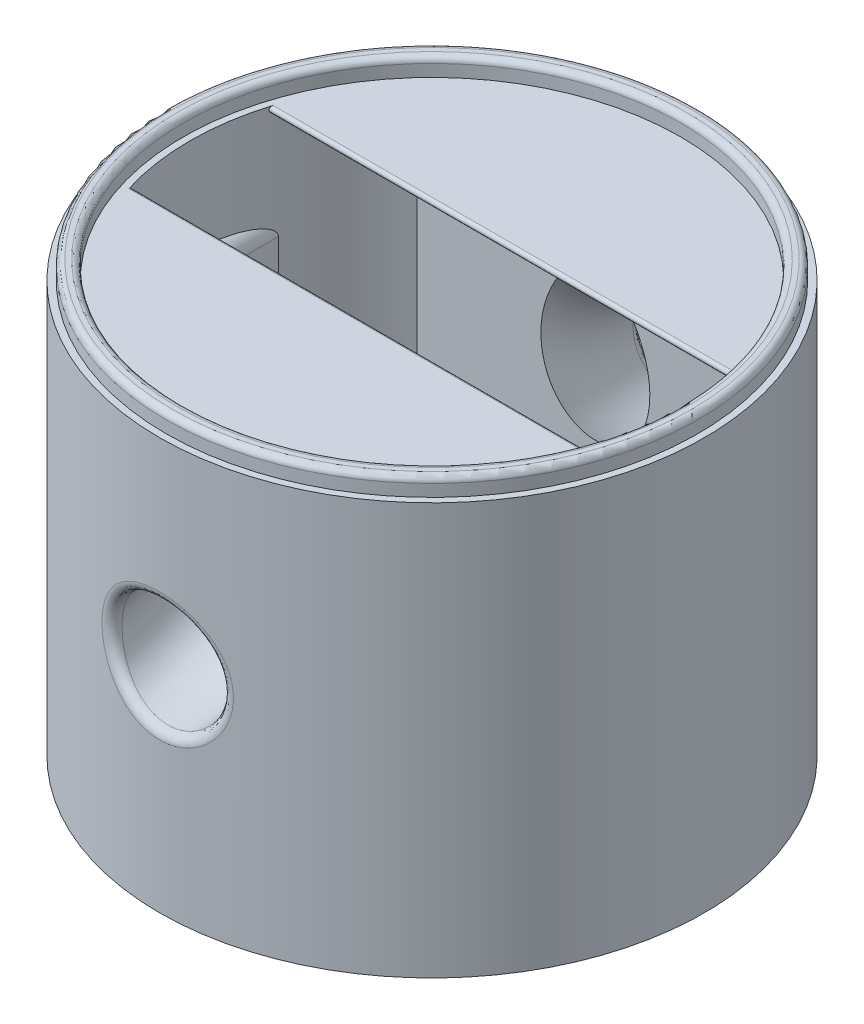
SolidWorks part; units mm, degrees
ref_plane "Płaszczyzna przednia" through (0, 0, 0) normal (0, 0, 1) x (1, 0, 0)
ref_plane "Płaszczyzna górna" through (0, 0, 0) normal (0, 1, 0) x (1, 0, 0)
ref_plane "Płaszczyzna prawa" through (0, 0, 0) normal (1, 0, 0) x (0, 0, -1)
sketch "Sketch1" plane through (0, 0, 0) normal (0, 1, 0) x (1, 0, 0)
  circle A0 centre (0, 0) radius 45
extrude "Boss-Extrude1" add sketch "Sketch1" along normal blind 35
sketch "Sketch19" plane through (0, 35, 0) normal (0, 1, 0) x (1, 0, 0)
  circle A0 centre (0, 0) radius 40
extrude "Cut-Extrude1" cut sketch "Sketch19" against normal blind 56
sketch "Sketch20" plane through (0, 35, 0) normal (0, 1, 0) x (1, 0, 0)
  line L0 (0, 0) -> (-40, 0)
  line L1 (-40, 0) -> (-40, 15)
  line L2 (-40, 15) -> (-37.9667, 15)
  line L3 (-37.9667, 15) -> (-37.9667, -15.0048)
  line L4 (0, 0) -> (0, -15.0048)
  line L5 (-37.9667, -15.0048) -> (-40, -15.0048)
  line L6 (-37.9667, -15.0048) -> (-37.9667, 15)
  line L7 (-37.9667, 15) -> (-40, 15)
  line L8 (-40, -15.0048) -> (-40, 15)
  line L9 (40, 15) -> (37.9667, 15)
  line L10 (37.9667, 15) -> (37.9667, -15.0048)
  line L11 (40, -15.0048) -> (40, 15)
  line L12 (37.9667, -15.0048) -> (40, -15.0048)
  line L13 (0, 0) -> (-15, 0)
  line L14 (-15, 0) -> (-15, -40)
  line L15 (-15, -40) -> (15, -40)
  line L16 (15, -40) -> (15, 40)
  line L17 (-15, 40) -> (-15, 0)
  line L18 (15, 40) -> (-15, 40)
  line L19 (0, 0) -> (0, -10)
  line L20 (0, 0) -> (0, -11)
  line L21 (0, -11) -> (15, -11)
  line L22 (15, -11) -> (15, 11)
  line L23 (15, 11) -> (-15, 11)
  line L24 (-15, 11) -> (-15, -11)
  line L25 (-15, -11) -> (0, -11)
  line L26 (15, -11) -> (15, 11)
  line L28 (-15, -11) -> (15, -11)
  line L29 (-15, -11) -> (-15, -40)
  line L30 (-15, -40) -> (15, -40)
  line L31 (15, -11) -> (15, -40)
  line L32 (15, 40) -> (-15, 40)
  line L33 (15, 40) -> (15, 11)
  line L34 (15, 11) -> (-15, 11)
  line L35 (-15, 40) -> (-15, 11)
  circle A0 centre (0, 0) radius 40 construction
  circle M8 centre (0, 0) radius 40
  dimension "D1" = 40
  dimension "D2" = 40
extrude "Boss-Extrude29" add sketch "Sketch20" along normal blind 1 and the other way blind 10 contours L3 L0 M8 | L8 L5 L3 M8 | L3 L2 L1 M8 | L3 L0 M8 | L10 L12 L11 L9
sketch "Sketch21" plane through (0, 35, 0) normal (0, 1, 0) x (1, 0, 0)
  line L0 (-0.2322, 0) -> (-15.2322, 0)
  line L1 (-0.2322, 0) -> (14.7678, 0)
  line L2 (-15.2322, 0) -> (-15.2322, -40)
  line L3 (-15.2322, -40) -> (14.7678, -40)
  line L4 (14.7678, -40) -> (14.7678, 40)
  line L5 (14.7678, 40) -> (-15.2322, 40)
  line L6 (-15.2322, 40) -> (-15.2322, 0)
  line L7 (14.7678, 0) -> (14.7678, 10.5)
  line L8 (14.7678, 10.5) -> (-15.2322, 10.5)
  line L9 (-15.2322, 10.5) -> (-15.2322, -10.5)
  line L10 (-15.2322, -10.5) -> (14.7678, -10.5)
  line L12 (14.7678, -40) -> (-15.2322, -40)
  line L13 (14.7678, -40) -> (14.7678, -10.5)
  line L14 (14.7678, -10.5) -> (-15.2322, -10.5)
  line L15 (-15.2322, -40) -> (-15.2322, -10.5)
  line L16 (-15.2322, 40) -> (14.7678, 40)
  line L17 (-15.2322, 40) -> (-15.2322, 10.5)
  line L18 (-15.2322, 10.5) -> (14.7678, 10.5)
  line L19 (14.7678, 40) -> (14.7678, 10.5)
sketch "Sketch23" plane through (0, 35, 0) normal (0, 1, 0) x (1, 0, 0)
  circle A0 centre (0, 0) radius 45
  circle A1 centre (0, 0) radius 40
extrude "Boss-Extrude32" add sketch "Sketch23" along normal blind 17
sketch "Sketch24" plane through (-37.9667, 0, 0) normal (1, 0, 0) x (0, 0, -1)
  line L0 (-12.5907, 36) -> (-12.5907, 25) construction
  line L1 (-12.5907, 36) -> (12.5907, 36)
  line L2 (-12.5907, 36) -> (-12.5907, 25)
  line L3 (-12.5907, 25) -> (12.5907, 25)
  line L4 (12.5907, 36) -> (12.5907, 25)
  line L5 (12.5907, 36) -> (-12.5907, 36) construction
  line L6 (-12.5907, 25) -> (12.5907, 25) construction
  line L7 (12.5907, 25) -> (12.5907, 36) construction
  line L8 (-12.5907, 36) -> (12.5907, 25)
  line L9 (0, 30.5) -> (0, 17)
  line L14 (0, 17) -> (-42.6389, 17)
  line L19 (-42.6389, 17) -> (-42.6389, 52)
  line L20 (40, 52) -> (-40, 52) construction
  line L21 (0, 16.95) -> (42.969, 16.95)
  line L23 (42.969, 16.95) -> (-42.6389, 16.95)
  line L24 (42.969, 16.95) -> (42.969, 52)
  line L25 (42.969, 52) -> (-42.6389, 52)
  line L26 (-42.6389, 16.95) -> (-42.6389, 52)
  circle A1 centre (0, 17) radius 36
extrude "Boss-Extrude37" add sketch "Sketch24" along normal blind 80 and the other way blind 5 contours A1 L25 L26 | A1 L24 L25
sketch "Sketch25" plane through (0, 52, 0) normal (0, 1, 0) x (1, 0, 0)
  circle A0 centre (0, 0) radius 9
extrude "Cut-Extrude2" cut sketch "Sketch25" against normal blind 4
sketch "Sketch28" plane through (0, 0, 0) normal (0, -1, 0) x (1, 0, 0)
  circle A0 centre (0, 0) radius 81.8752
  circle A1 centre (0, 0) radius 45
extrude "Cut-Extrude3" cut sketch "Sketch28" against normal blind 125 contours A0 | A1
sketch "Sketch29" plane through (0, 52, 0) normal (0, 1, 0) x (1, 0, 0)
  line L0 (0, 0) -> (-9.1, 0)
  line L1 (-9.1, 0) -> (-9.1, -48)
  line L2 (-9.1, 42.2639) -> (9.1, 42.2639)
  line L3 (-9.1, -48) -> (9.1, -48)
  line L4 (-9.1, -48) -> (-9.1, -42.2639)
  line L5 (-9.1, -42.2639) -> (9.1, -42.2639)
  line L6 (9.1, -48) -> (9.1, -42.2639)
  line L7 (9.1, 48) -> (9.1, 42.2639)
  line L8 (-9.1, 48) -> (9.1, 48)
  line L9 (-9.1, 48) -> (-9.1, 42.2639)
  circle M15 centre (0, 0) radius 45
extrude "Boss-Extrude38" add sketch "Sketch29" against normal blind 52 contours L8 L9 L7 M15 | L3 L6 L1 M15 | L9 L2 L7 M15 | L6 L5 L1 M15
sketch "Sketch32" plane through (0, 0, 48) normal (0, 0, 1) x (1, 0, 0)
  line L0 (0, 0) -> (-66.2271, 0)
  line L1 (-9.1, 0) -> (9.1, 0) construction
  line L3 (-66.2271, 0) -> (66.2271, 0)
  line L4 (-66.2271, 0) -> (-66.2271, 45.6022)
  line L5 (-66.2271, 45.6022) -> (66.2271, 45.6022)
  line L6 (66.2271, 0) -> (66.2271, 45.6022)
  line M6 (-9.1, 52) -> (-9.1, 0)
  line M7 (-9.1, 0) -> (9.1, 0)
  line M8 (9.1, 0) -> (9.1, 52)
extrude "Boss-Extrude41" add sketch "Sketch32" against normal blind 21 contours L5 L4 L0 M6 | L5 M6 M7 M8 | L3 L6 L5 M8
sketch "Sketch30" plane through (0, 0, 48) normal (0, 0, 1) x (1, 0, 0)
  line L0 (-9.1, 19) -> (9.1, 19)
  line L1 (-9.1, 45.6022) -> (-9.1, 52) construction
  line L2 (9.1, 52) -> (9.1, 45.6022) construction
  line L3 (0, 19) -> (0, 25.0181)
  line L4 (0, 25.0181) -> (7.01, 25.0181)
  line L5 (7.01, 25.0181) -> (-5.4249, 25.0181)
  line L6 (0, 19) -> (0, 0)
  circle A0 centre (0, 19) radius 9
revolve "Cut-Revolve4" cut sketch "Sketch30" angle 62
sketch "Sketch33" plane through (0, 0, -48) normal (0, 0, -1) x (-1, 0, 0)
  line L0 (0, 0) -> (68.0647, 0)
  line L2 (68.0647, 0) -> (-74.072, 0)
  line L3 (68.0647, 0) -> (68.0647, 43.8772)
  line L4 (68.0647, 43.8772) -> (-74.072, 43.8772)
  line L5 (-74.072, 0) -> (-74.072, 43.8772)
  line M6 (-9.1, 52) -> (-9.1, 0)
  line M7 (-9.1, 0) -> (9.1, 0)
  line M8 (9.1, 0) -> (9.1, 52)
extrude "Boss-Extrude42" add sketch "Sketch33" against normal blind 21 contours L5 L2 L4 M6 | L3 L4 L0 M8 | L4 M8 M6 M7
sketch "Sketch34" plane through (0, 0, -48) normal (0, 0, -1) x (-1, 0, 0)
  line L0 (9.1, 43.8772) -> (9.1, 0)
  line L1 (36, 43.8772) -> (9.1, 43.8772) construction
  line L2 (9.1, 43.8772) -> (9.1, 52) construction
  line L3 (68.0647, 0) -> (-74.072, 0) construction
  line L4 (-9.1, 43.8772) -> (-9.1, 0)
  line L5 (-9.1, 43.8772) -> (-36, 43.8772) construction
  line L6 (-9.1, 52) -> (-9.1, 43.8772) construction
  line L7 (0, 0) -> (0, 19)
  circle A0 centre (0, 19) radius 9
revolve "Cut-Revolve5" cut sketch "Sketch34" angle 63
sketch "Sketch35" plane through (0, 52, 0) normal (0, 1, 0) x (1, 0, 0)
  circle A0 centre (0, 0) radius 102.54
  circle A1 centre (0, 0) radius 45
extrude "Cut-Extrude4" cut sketch "Sketch35" against normal blind 136
sketch "Sketch37" plane through (0, 0, 0) normal (0, -1, 0) x (1, 0, 0)
  line L0 (-29.5127, 27) -> (29.5127, 27)
  line L1 (-29.5127, 27) -> (29.5127, 27) construction
  line L2 (29.5127, 27) -> (-29.5127, 27) construction
  line L3 (-29.5127, -27) -> (29.5127, -27)
  line L4 (-29.5127, -27) -> (29.5127, -27) construction
  circle A1 centre (0, 0) radius 45
  arc A2 (-29.5127, 27) -> (-29.5127, -27) centre (0, 0) ccw construction
  arc A3 (-39.1024, -8.4261) -> (-29.5127, -27) centre (0, 0) ccw construction
  circle A4 centre (0, 0) radius 40
  arc M2 (29.5127, 27) -> (29.5127, -27) centre (0, 0) cw
  line M3 (29.5127, -27) -> (-29.5127, -27)
  arc M4 (-29.5127, -27) -> (-29.5127, 27) centre (0, 0) cw
  line M5 (-29.5127, 27) -> (29.5127, 27)
  circle M6 centre (0, 0) radius 45
extrude "Boss-Extrude43" add sketch "Sketch37" along normal blind 16 contours A4 M6 M2 M4 | A4 M3 | A4 M5
sketch "Sketch38" plane through (0, 52, 0) normal (0, 1, 0) x (1, 0, 0)
  circle A0 centre (0, 0) radius 41.1
  circle A1 centre (0, 0) radius 43.9
extrude "Boss-Extrude44" add sketch "Sketch38" along normal blind 3
sketch "Sketch39" plane through (0, -16, 0) normal (0, -1, 0) x (1, 0, 0)
  line L0 (0, 0) -> (0, 33)
  line L1 (0, 0) -> (15.6861, 0)
  line L2 (3.3486, 33) -> (1.6743, 35.9)
  line L3 (1.6743, 35.9) -> (-1.6743, 35.9)
  line L4 (-1.6743, 35.9) -> (-3.3486, 33)
  line L5 (-3.3486, 33) -> (-1.6743, 30.1)
  line L6 (-1.6743, 30.1) -> (1.6743, 30.1)
  line L7 (1.6743, 30.1) -> (3.3486, 33)
  line L8 (-3.3486, -33) -> (-1.6743, -30.1)
  line L9 (-1.6743, -30.1) -> (1.6743, -30.1)
  line L10 (1.6743, -30.1) -> (3.3486, -33)
  line L11 (3.3486, -33) -> (1.6743, -35.9)
  line L12 (1.6743, -35.9) -> (-1.6743, -35.9)
  line L13 (-1.6743, -35.9) -> (-3.3486, -33)
  line L14 (-1.6743, -30.1) -> (1.6743, -35.9)
  circle A0 centre (0, 33) radius 2.9 construction
  dimension "D1" = 2.9
  dimension "D2" = 2.9
extrude "Cut-Extrude5" cut sketch "Sketch39" against normal blind 4.5
sketch "Sketch40" plane through (0, -16, 0) normal (0, -1, 0) x (1, 0, 0)
  line L0 (0, 0) -> (0, -28.7604)
  line L1 (0, -28.7604) -> (-5.1121, -28.7604)
  line L2 (-5.1121, -28.7604) -> (-5.1121, -38.9306)
  line L3 (-5.1121, -38.9306) -> (5.428, -38.9306)
  line L4 (5.428, -38.9306) -> (5.428, -28.7604)
  line L5 (5.428, -28.7604) -> (0, -28.7604)
  line L6 (0, 0) -> (7.5545, 0)
  line L7 (5.428, 28.7604) -> (0, 28.7604)
  line L8 (5.428, 38.9306) -> (5.428, 28.7604)
  line L9 (-5.1121, 38.9306) -> (5.428, 38.9306)
  line L10 (-5.1121, 28.7604) -> (-5.1121, 38.9306)
  line L11 (0, 28.7604) -> (-5.1121, 28.7604)
  line M7 (1.6743, 30.1) -> (-1.6743, 30.1)
  line M8 (-1.6743, 30.1) -> (-3.3486, 33)
  line M9 (-3.3486, 33) -> (-1.6743, 35.9)
  line M10 (-1.6743, 35.9) -> (1.6743, 35.9)
  line M11 (1.6743, 35.9) -> (3.3486, 33)
  line M12 (3.3486, 33) -> (1.6743, 30.1)
  line M18 (-3.3486, -33) -> (-1.6743, -30.1)
  line M19 (-1.6743, -30.1) -> (1.6743, -30.1)
  line M20 (1.6743, -30.1) -> (3.3486, -33)
  line M21 (3.3486, -33) -> (1.6743, -35.9)
  line M22 (1.6743, -35.9) -> (-1.6743, -35.9)
  line M23 (-1.6743, -35.9) -> (-3.3486, -33)
extrude "Boss-Extrude45" add sketch "Sketch40" against normal blind 2 contours M18 M23 M22 M21 M20 M19 | L4 L5 L1 L2 L3 M23 M18 M19 M20 M21 M22 | L11 L7 L8 L9 L10 M12 M7 M8 M9 M10 M11 | M7 M12 M11 M10 M9 M8
sketch "Sketch41" plane through (0, -16, 0) normal (0, -1, 0) x (1, 0, 0)
  line L0 (0, 0) -> (0, 33)
  line L1 (0, 0) -> (10.1881, 0)
  circle A0 centre (0, 33) radius 1.7
  circle A1 centre (0, -33) radius 1.7
extrude "Cut-Extrude6" cut sketch "Sketch41" against normal blind 10
fillet "Fillet3" radius 3 4 edges at (-37.9667, 25, 0) (-37.9667, 36, 0) (37.9667, 25, 0) (37.9667, 36, 0)
fillet "Fillet4" radius 1.5 2 edges at (7.3181, 24.4731, 44.401) (4.5617, 26.966, -44.7682)
fillet "Fillet5" radius 0.5 2 edges at (0, 40.8118, 27) (0, 40.8118, -27)
fillet "Fillet6" radius 0.5 10 edges at (-21.1324, 52, 8.4261) (35.3801, 47.7856, 18.6613) (21.1324, 52, -8.4261) (35.3801, 47.7856, -18.6613) (-21.1324, 52, -8.4261) (-0.2781, 51.858, -8.9957) (21.1324, 52, 8.4261) (-0.2781, 51.858, 8.9957) (0, 52, 9) (0, 52, -9)
fillet "Fillet7" radius 1 2 edges at (0, 55, 41.1) (0, 55, 43.9)
